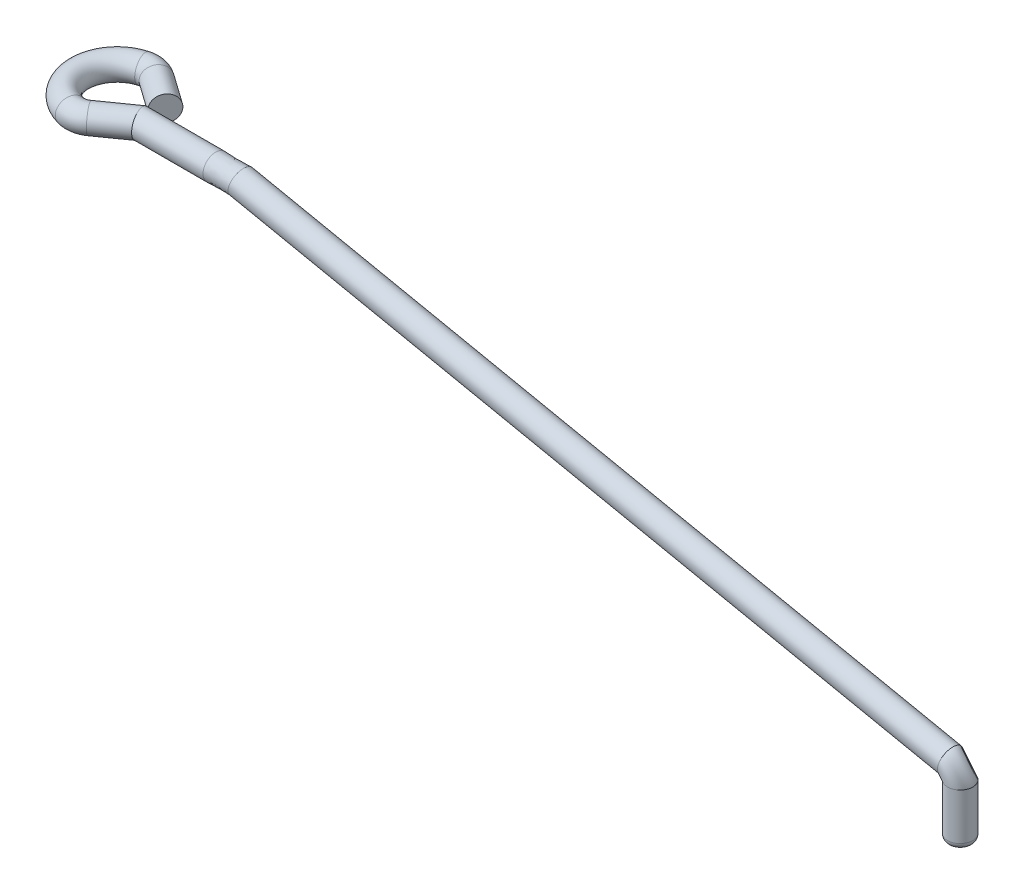
SolidWorks part; units mm, degrees
ref_plane "Front Plane" through (0, 0, 0) normal (0, 0, 1) x (1, 0, 0)
ref_plane "Top Plane" through (0, 0, 0) normal (0, 1, 0) x (1, 0, 0)
ref_plane "Right Plane" through (0, 0, 0) normal (1, 0, 0) x (0, 0, -1)
sketch "Sketch1" plane through (0, 0, 0) normal (0, 0, 1) x (1, 0, 0)
  line L0 (34, -2.5) -> (34, -0.5)
  dimension "D1" = 34
  dimension "D2" = 2
  dimension "D3" = 0.5
sweep "Sweep1" add path "Sketch1" circular profile diameter 1 parameters "D3"=1
ref_plane "Plane1" through (0, 5.9, 0) normal (0, 1, 0) x (1, 0, 0)
sketch "Sketch2" plane through (0, 5.9, 0) normal (0, 1, 0) x (1, 0, 0)
  line L0 (0.233, -0.8352) -> (1.4142, 0)
  line L1 (0.233, 1.8352) -> (1.4142, 1)
  line L2 (1.4142, 0) -> (4.4142, 0)
  line L3 (0, -1) -> (0.233, -0.8352) construction
  line L4 (0, 2) -> (0.233, 1.8352) construction
  line L5 (1.4142, 1) -> (1.4142, 0) construction
  line L6 (0, -1) -> (0, 0) construction
  line L7 (0, 0) -> (1.4142, 0) construction
  arc A0 (1.4142, 0) -> (1.4142, 1) centre (0, 0.5) ccw construction
  arc A1 (-0.4, -0.9457) -> (0.233, -0.8352) centre (-0.2, -0.2228) ccw
  arc A2 (-0.4, 1.9457) -> (0.233, 1.8352) centre (-0.2, 1.2228) cw
  arc A3 (-0.4, 1.9457) -> (-0.4, -0.9457) centre (0, 0.5) ccw
  arc A4 (0, -1) -> (1.4142, 0) centre (0, 0.5) ccw construction
  arc A5 (1.4142, 1) -> (0, 2) centre (0, 0.5) ccw construction
  dimension "D1" = 3
  dimension "D3" = 0.75
  dimension "D2" = 1
  dimension "D4" = 3
sweep "Sweep2" add path "Sketch2" circular profile diameter 1 parameters "D3"=1
sketch "Sketch3" plane through (0, 0, 0) normal (0, 0, 1) x (1, 0, 0)
  line L0 (5.4142, 5.9) -> (33.6011, 0.0823)
  line L1 (34, -0.4073) -> (34, -0.5)
  line L2 (34.5, -0.5) -> (33.5, -0.5) construction
  line L3 (1.4142, 5.9) -> (4.4142, 5.9) construction
  line L5 (4.4142, 5.4) -> (4.4142, 6.4) construction
  arc A0 (33.6011, 0.0823) -> (34, -0.4073) centre (33.5, -0.4073) cw
  point P18 (34, 0)
  dimension "D2" = 0.5
  dimension "D1" = 0.5
  dimension "D3" = 1
sweep "Sweep3" add path "Sketch3" circular profile diameter 1 parameters "D3"=1
loft "Loft1" add section face at (4.4142, 5.9, 0.5) section face at (5.4142, 5.9, 0.5) connector at (4.4142, 5.4682, 0.2521) connector at (5.3136, 5.4123, 0.0452)
fillet "Fillet2" radius 0.25 1 edges at (34, -2.5, 0.5)
ref_plane "Plane2" through (0, 0, -0.5) normal (0, 0, 1) x (1, 0, 0)
